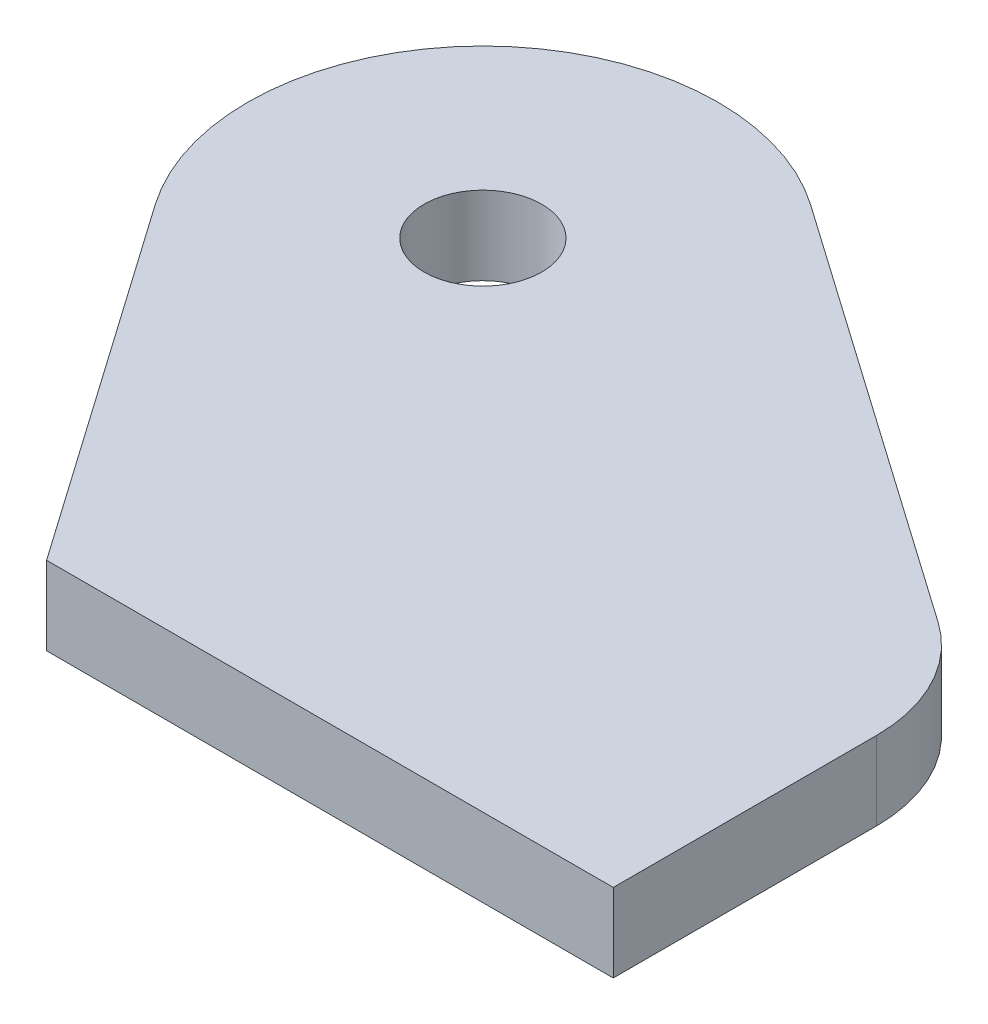
SolidWorks part; units mm, degrees
ref_plane "Front Plane" through (0, 0, 0) normal (0, 0, 1) x (1, 0, 0)
ref_plane "Top Plane" through (0, 0, 0) normal (0, 1, 0) x (1, 0, 0)
ref_plane "Right Plane" through (0, 0, 0) normal (1, 0, 0) x (0, 0, -1)
sketch "Sketch1" plane through (0, 0, 0) normal (0, 1, 0) x (1, 0, 0)
  line L0 (19.05, 63.5) -> (19.05, 0) construction
  line L5 (19.05, 0) -> (109.7374, 0)
  line L6 (64.4344, 31.7215) -> (29.9766, 55.8491)
  line L8 (3.4452, 29.3176) -> (23.9736, 0)
  line L10 (69.85, 21.3183) -> (69.85, 0)
  arc A1 (29.9766, 55.8491) -> (0, 40.2442) centre (19.05, 40.2442) ccw
  circle A2 centre (19.05, 40.2442) radius 4.7625
  arc A3 (29.9766, 55.8491) -> (3.4452, 29.3176) centre (19.05, 40.2442) ccw
  arc A4 (69.85, 21.3183) -> (64.4344, 31.7215) centre (57.15, 21.3183) ccw
  dimension "D3" = 38.1
  dimension "D5" = 9.525
  dimension "D10" = 12.7
  dimension "D1" = 35
  dimension "D2" = 63.5
  dimension "D4" = 55.8491
  dimension "D6" = 55
  dimension "D7" = 19.05
  dimension "D8" = 40.2442
  dimension "D9" = 50.8
extrude "Boss-Extrude1" add sketch "Sketch1" along normal blind 6.35 contours A1 L0 A2 L8 L5 L6 | L0 A3 L8 A2 region at (41.6909, 0, -23.649) region at (11.1354, 0, -37.1362)
